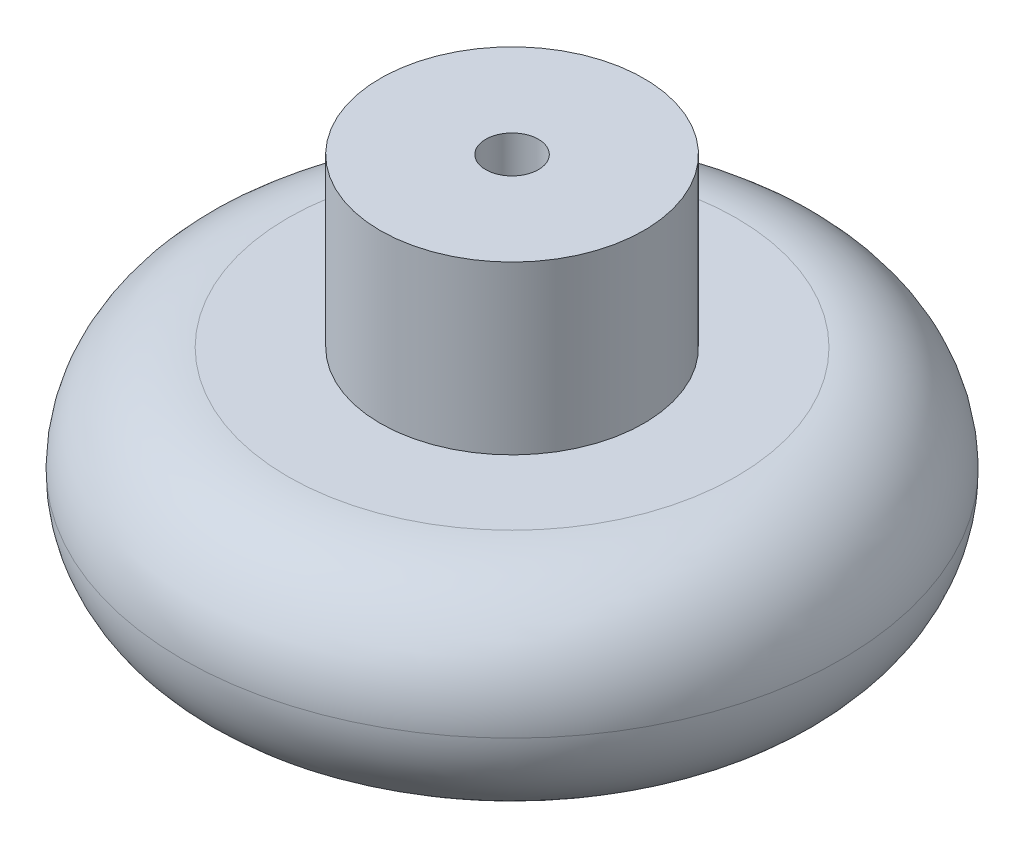
SolidWorks part; units mm, degrees
material "聚亚安酯(11671)"
ref_plane "前视基准面" through (0, 0, 0) normal (0, 0, 1) x (1, 0, 0)
ref_plane "上视基准面" through (0, 0, 0) normal (0, 1, 0) x (1, 0, 0)
ref_plane "右视基准面" through (0, 0, 0) normal (1, 0, 0) x (0, 0, -1)
sketch "草图1" plane through (0, 0, 0) normal (0, 1, 0) x (1, 0, 0)
  circle A0 centre (0, 0) radius 37.5
  dimension "D1" = 75
extrude "凸台-拉伸1" add sketch "草图1" along normal blind 24
sketch "草图3" plane through (0, 24, 0) normal (0, 1, 0) x (1, 0, 0)
  circle A0 centre (0, 0) radius 15
  dimension "D1" = 30
extrude "凸台-拉伸2" add sketch "草图3" along normal blind 19
hole_wizard "Ø6.0 (6) 直径孔1" positions "草图6" profile "草图5" hole size "Ø6.0" standard "GB"
sketch "草图6" plane through (0, 43, 0) normal (0, 1, 0) x (1, 0, 0)
  point P0 (0, 0)
sketch "草图5" plane through (0, 43, 0) normal (1, 0, 0) x (0, 0, 1)
  line L0 (0, 0) -> (0, 16.8026)
  line L1 (0, 16.8026) -> (3, 15)
  line L2 (3, 15) -> (3, 0)
  line L5 (3, 0) -> (0, 0)
  line L10 (0, 16.8026) -> (-3, 15) construction
  line L11 (0, -6.35) -> (0, 107.95) construction
  dimension "孔直径" = 6
  dimension "孔深度" = 15
  dimension "导头角度" = 118
fillet "圆角1" radius 12 2 edges at (0, 0, 37.5) (0, 24, 37.5)
hole_wizard "M6 螺纹孔的螺纹孔钻头2" positions "3D草图3" profile "草图8" hole size "M6" standard "GB"
sketch3d "3D草图3"
  point P0 (-4.613, 32.9898, -14.2731)
sketch "草图8" plane through (-4.613, 32.9898, -14.2731) normal (0, 1, 0) x (-0.9515, 0, 0.3075)
  line L0 (0, 0) -> (0, 16.5022)
  line L1 (0, 16.5022) -> (2.5, 15)
  line L2 (2.5, 15) -> (2.5, 0)
  line L5 (2.5, 0) -> (0, 0)
  line L10 (0, 16.5022) -> (-2.5, 15) construction
  line L11 (0, -6.35) -> (0, 107.95) construction
  dimension "孔直径" = 5
  dimension "孔深度" = 15
  dimension "导头角度" = 118
